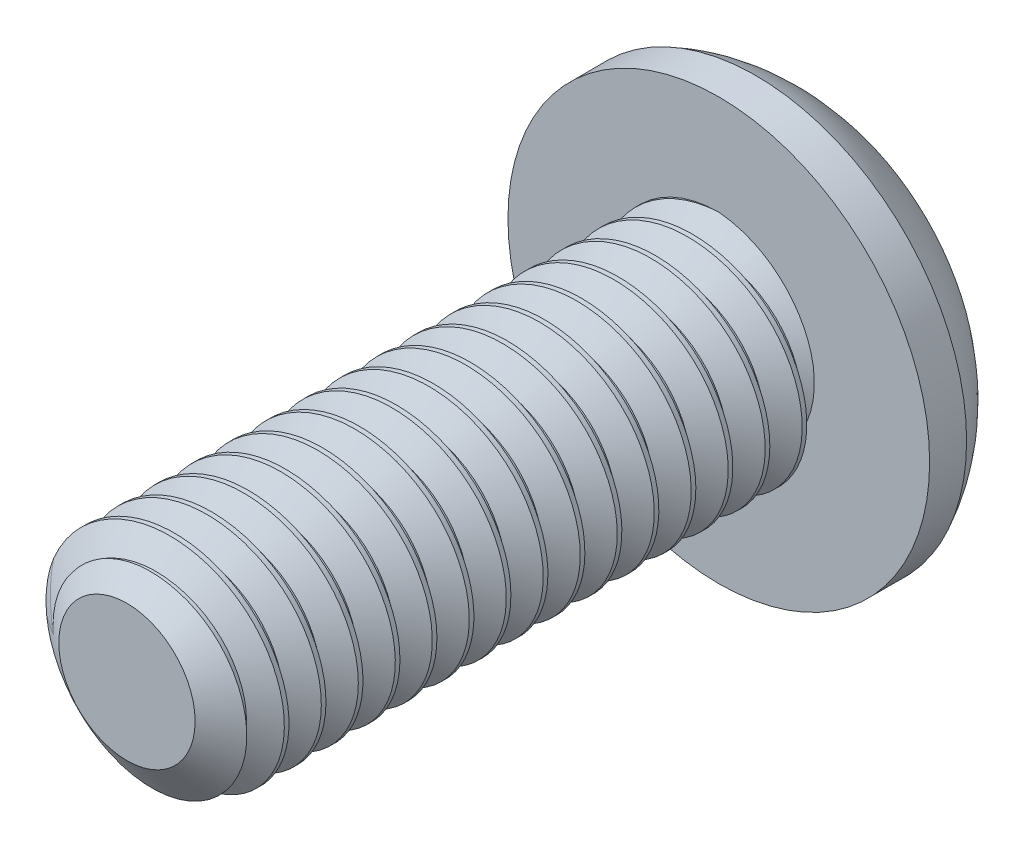
SolidWorks part; units mm, degrees
material "Plain Carbon Steel"
ref_plane "Front Plane" through (0, 0, 0) normal (0, 0, 1) x (1, 0, 0)
ref_plane "Top Plane" through (0, 0, 0) normal (0, 1, 0) x (1, 0, 0)
ref_plane "Right Plane" through (0, 0, 0) normal (1, 0, 0) x (0, 0, -1)
sketch "Sketch1" plane through (0, 0, 0) normal (0, 0, 1) x (1, 0, 0)
  circle A0 centre (0, 0) radius 1.5
  dimension "OD" = 3
extrude "Extrude1" add sketch "Sketch1" against normal blind 8
sketch "Sketch2" plane through (0, 0, 0) normal (0, 0, 1) x (1, 0, 0)
  circle A0 centre (0, 0) radius 1.5 construction
  circle A1 centre (0, 0) radius 1.5
curve "Helix/Spiral1" pitch 0.5 height 8.5 radius 1.5 centre (0, 0, 0) axis (0, 0, -1) start towards (0, 1, 0) parameters "pitch"=0.5
sketch "Sketch3" plane through (0, 0, 0) normal (1, 0, 0) x (0, 0, -1)
  line L0 (-0.4375, 1.5) -> (-0.25, 1.1752)
  line L1 (-0.25, 1.1752) -> (-0.1875, 1.1752)
  line L2 (-0.1875, 1.1752) -> (0, 1.5)
  line L3 (-0.4375, 1.5) -> (0, 1.5)
  line L4 (-0.2187, 1.5) -> (-0.2187, 1.1752) construction
  line L5 (-0.3437, 1.3376) -> (-0.0937, 1.3376) construction
  line L6 (0, 1.5) -> (0, -1.5) construction
  dimension "D1" = 0.0625
  dimension "D2" = 0.25
  dimension "D3" = 60
sweep "Cut-Sweep1" cut profiles "Sketch3" path "Helix/Spiral1"
sketch "Sketch4" plane through (0, 0, 0) normal (1, 0, 0) x (0, 0, -1)
  line L0 (0.4053, 1.5) -> (0, 0.9212)
  line L1 (0, 0.9212) -> (0, 1.5)
  line L2 (0.4053, 1.5) -> (0, 1.5)
  line L3 (-0.4375, 1.5) -> (0, 1.5) construction
  line L4 (0, 0) -> (7.0209, 0) construction
  dimension "D1" = 55
  dimension "D2" = 0.254
revolve "Cut-Revolve1" cut sketch "Sketch4" angle 360 about L4
sketch "Sketch5" plane through (0, 0, 0) normal (1, 0, 0) x (0, 0, -1)
  line L0 (8, -1.1822) -> (8, 1.0703) construction
  line L1 (8, 1.627) -> (28.1202, 1.627)
  line L2 (8, 1.627) -> (8, 0)
  line L3 (8, 0) -> (28, 0)
  line L4 (28, 1.2968) -> (28, 0)
  line L5 (28.1202, 1.627) -> (28, 1.2968)
  line L6 (0, 0) -> (9.9695, 0) construction
  point P3 (28, 1.627)
  point P10 (28, 1.627)
  dimension "D1" = 0.3302
  dimension "Thread min" = 28
  dimension "D2" = 0.127
  dimension "D3" = 20
revolve "partially thread" [suppressed] add sketch "Sketch5" angle 360 about L6
sketch "Sketch6" plane through (0, 0, -8) normal (0, 0, -1) x (-1, 0, 0)
  circle A0 centre (0, 0) radius 2.85
  dimension "head dia" = 5.7
extrude "Extrude2" add sketch "Sketch6" along normal blind 1.65
sketch "Sketch10" plane through (0, 0, 0) normal (1, 0, 0) x (0, 0, -1)
  line L0 (9.65, -2.85) -> (9.65, 2.85) construction
  line L1 (0, 0) -> (15.9584, 0) construction
  line L2 (9.65, 2.85) -> (8, 2.85) construction
  line L3 (8, 2.85) -> (8, -2.85) construction
  line L4 (8.5, 2.85) -> (8.5, 3.35)
  line L5 (8.5, 3.35) -> (10.15, 3.35)
  line L6 (10.15, 3.35) -> (10.15, 1)
  line L7 (9.65, 1) -> (10.15, 1)
  arc A0 (9.65, 1) -> (8.5, 2.85) centre (7.587, 1) ccw
  dimension "D1" = 2
  dimension "D2" = 0.5
  dimension "D3" = 0.5
revolve "Cut-Revolve2" cut sketch "Sketch10" angle 360 about L1
ref_plane "Plane1" through (0, 0, -9.65) normal (0, 0, 1) x (1, 0, 0)
sketch "Sketch7" plane through (0, 0, -9.65) normal (0, 0, -1) x (-1, 0, 0)
  line L1 (0, 1.1547) -> (-1, 0.5774)
  line L2 (-1, 0.5774) -> (-1, -0.5774)
  line L3 (-1, -0.5774) -> (0, -1.1547)
  line L4 (0, -1.1547) -> (1, -0.5774)
  line L5 (1, -0.5774) -> (1, 0.5774)
  line L6 (1, 0.5774) -> (0, 1.1547)
  circle A0 centre (0, 0) radius 1 construction
  dimension "hex dia" = 2
extrude "Cut-Extrude1" cut sketch "Sketch7" against normal blind 1.5
sketch "Sketch8" plane through (0, 0, -9.65) normal (0, 0, 1) x (1, 0, 0)
  circle A0 centre (0, 0) radius 1.1547
extrude "Cut-Extrude2" cut sketch "Sketch8" along normal through all draft 45
sketch "Sketch9" plane through (0, 0, 0) normal (1, 0, 0) x (0, 0, -1)
  line L0 (0, 1.5) -> (0, -1.5) construction
  line L1 (2.75, 1.5) -> (2.75, -1.5) construction
  dimension "D1" = 2.75
equation "\"D3@Helix/Spiral1\" = \"screw length@Extrude1\"+\"pitch@Helix/Spiral1\""
equation "\"D1@Sketch3\" = \"pitch@Helix/Spiral1\"*.125"
equation "\"D2@Sketch3\" = \"pitch@Helix/Spiral1\"*.5"
equation "\"D1@Cut-Extrude1\" = \"hex dia@Sketch7\"*.75"
equation "\"D1@Sketch9\" = \"pitch@Helix/Spiral1\"*5.5"
equation "\"D1@Sketch10\" = \"hex dia@Sketch7\""
equation "\"D1@Plane1\" = \"head depth@Extrude2\""
